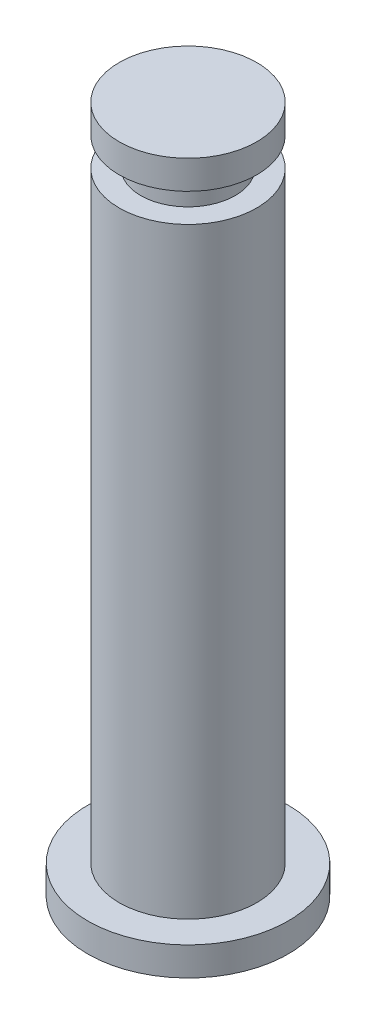
SolidWorks part; units mm, degrees
ref_plane "Alzado" through (0, 0, 0) normal (0, 0, 1) x (1, 0, 0)
ref_plane "Planta" through (0, 0, 0) normal (0, 1, 0) x (1, 0, 0)
ref_plane "Vista lateral" through (0, 0, 0) normal (1, 0, 0) x (0, 0, -1)
sketch "Croquis1" plane through (0, 0, 0) normal (0, 1, 0) x (1, 0, 0)
  circle A0 centre (0, 0) radius 3.5
  circle A1 centre (0, 0) radius 2.4
  dimension "D1" = 7
  dimension "D2" = 4.8
extrude "Saliente-Extruir1" add sketch "Croquis1" along normal blind 1
extrude "Saliente-Extruir2" add sketch "Croquis1<2>" along normal blind 24 contours A1 region at (0, 0, 0)
sketch "Croquis1<2>" plane through (0, 0, 0) normal (0, 1, 0) x (1, 0, 0) same geometry as "Croquis1"
sketch "Croquis2" plane through (0, 24, 0) normal (0, 1, 0) x (1, 0, 0)
  circle A0 centre (0, 0) radius 1.65
  circle A2 centre (0, 0) radius 2.4
  circle A3 centre (0, 0) radius 2.4
  dimension "D2" = 0.75
  dimension "D1" = 0
extrude "Cortar-Extruir1" cut sketch "Croquis2" against normal blind 1 from offset 1 offset against normal yes
